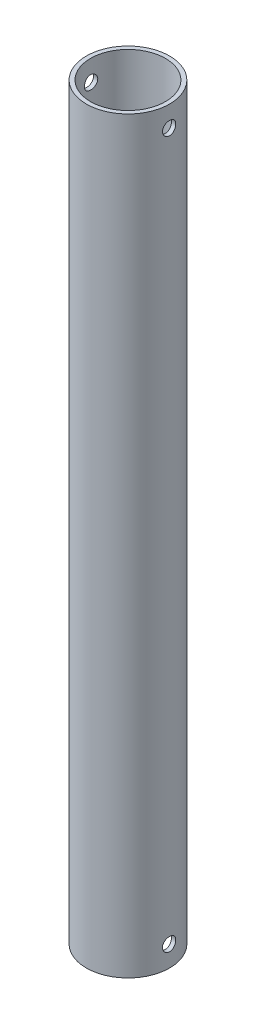
SolidWorks part; units mm, degrees
material "Toray T700"
ref_plane "Front" through (0, 0, 0) normal (0, 0, 1) x (1, 0, 0)
ref_plane "Top" through (0, 0, 0) normal (0, 1, 0) x (1, 0, 0)
ref_plane "Right" through (0, 0, 0) normal (1, 0, 0) x (0, 0, -1)
sketch "Sketch1" plane through (0, 0, 0) normal (0, 1, 0) x (1, 0, 0)
  line L5 (4.7969, 0) -> (-5.97, 0) construction
  circle A0 centre (0, 0) radius 10
  circle A1 centre (0, 0) radius 9
  dimension "D1" = 20
  dimension "D2" = 18
extrude "Boss-Extrude1" add sketch "Sketch1" along normal blind 179.7
ref_axis "Axis1" through (0, 179.7, 0) along (0, -1, 0)
ref_plane "Plane1" through (-10, 0, 0) normal (-1, 0, 0) x (0, 0, 1)
hole_wizard "M3 Clearance Hole1" positions "Sketch3" profile "Sketch2" hole size "M3" standard "DIN" end condition through all
sketch "Sketch3" plane through (-10, 0, 0) normal (-1, 0, 0) x (0, 0, 1)
  line L0 (-9, 0) -> (9, 0) construction
  line L1 (0, -50) -> (0, 50) construction
  point P0 (0, 5)
  dimension "D1" = 5
sketch "Sketch2" plane through (-10, 5, 0) normal (0, 1, 0) x (0, 0, 1)
  line L0 (0, 0) -> (0, 20)
  line L1 (0, 20) -> (1.6, 20)
  line L2 (1.6, 20) -> (1.6, 0)
  line L5 (1.6, 0) -> (0, 0)
  line L11 (0, -6.35) -> (0, 107.95) construction
  dimension "Thru Hole Dia." = 3.2
  dimension "Thru Hole Depth" = 20
ref_plane "Plane2" through (0, 89.85, 0) normal (0, 1, 0) x (1, 0, 0)
mirror "Mirror1" about plane through (0, 89.85, 0) normal (0, 1, 0) of "M3 Clearance Hole1"
